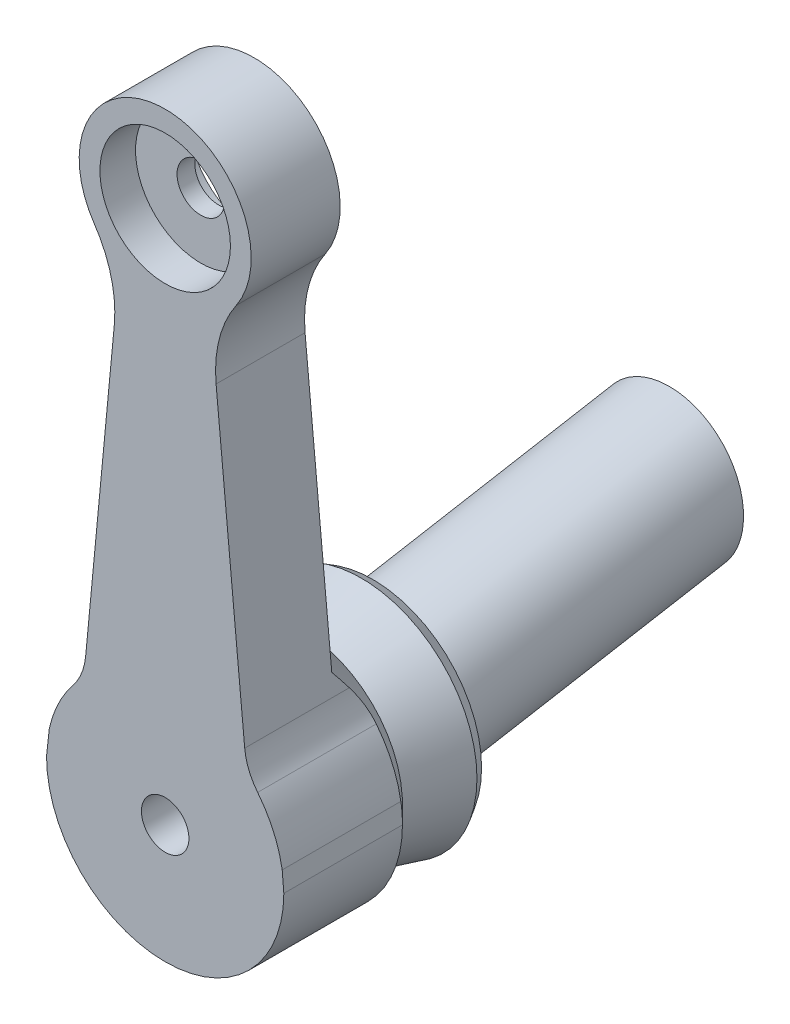
SolidWorks part; units mm, degrees
material "ABS"
ref_plane "Front Plane" through (0, 0, 0) normal (0, 0, 1) x (1, 0, 0)
ref_plane "Top Plane" through (0, 0, 0) normal (0, 1, 0) x (1, 0, 0)
ref_plane "Right Plane" through (0, 0, 0) normal (1, 0, 0) x (0, 0, -1)
sketch "Sketch2" plane through (0, 0, 0) normal (0, 0, 1) x (1, 0, 0)
  line L0 (0, 0) -> (0, 4) construction
  line L1 (19.7273, 3.2917) -> (20, 0)
  line L2 (0, 57.5) -> (0, 90) construction
  line L3 (-19.546, 4.2371) -> (-20, 0)
  line L4 (13.4071, 17.897) -> (7.9399, 75.3751)
  line L5 (-13.4071, 17.897) -> (-7.9399, 75.3751)
  arc A0 (-19.546, 4.2371) -> (19.7273, 3.2917) centre (0, 0) ccw
  circle A1 centre (0, 0) radius 4
  circle A2 centre (0, 90) radius 4
  arc A3 (12.5, 90) -> (-12.5, 90) centre (0, 90) ccw
  arc A4 (-15.5877, 12.531) -> (15.5877, 12.531) centre (0, 0) ccw
  arc A5 (9.9515, 82.4358) -> (-9.9515, 82.4358) centre (0, 90) ccw
  arc A6 (13.4071, 17.897) -> (15.5877, 12.531) centre (23.451, 18.8523) ccw
  arc A7 (-13.4071, 17.897) -> (-15.5877, 12.531) centre (-23.451, 18.8523) cw
  arc A8 (7.9399, 75.3751) -> (9.9515, 82.4358) centre (17.9838, 76.3305) cw
  arc A9 (-7.9399, 75.3751) -> (-9.9515, 82.4358) centre (-17.9838, 76.3305) ccw
  point P21 (13.7258, 14.5465)
  point P24 (-13.7258, 14.5465)
  point P27 (7.5, 80)
  point P30 (-7.5, 80)
  dimension "D1" = 40
  dimension "D2" = 8
  dimension "D4" = 8
  dimension "D5" = 25
  dimension "D6" = 25
  dimension "D8" = 10.0892
  dimension "D3" = 90
  dimension "D7" = 7.5
extrude "Boss-Extrude1" add sketch "Sketch2" along normal blind 15 contours L1 A3 L3 A0 A1 A2 region at (0.0012, 33.4788, 0)
sketch "Sketch3" plane through (0, 0, 0) normal (0, 0, -1) x (-1, 0, 0)
  circle A0 centre (0, 90) radius 11
  dimension "D1" = 22
extrude "Cut-Extrude1" cut sketch "Sketch3" against normal blind 6
sketch "Sketch4" plane through (0, 0, 15) normal (0, 0, 1) x (1, 0, 0)
  circle A0 centre (0, 90) radius 11
  dimension "D1" = 22
extrude "Cut-Extrude2" cut sketch "Sketch4" against normal blind 6
sketch "Sketch5" plane through (0, 0, 0) normal (0, 0, -1) x (-1, 0, 0)
  circle A0 centre (0, 0) radius 15
  dimension "D1" = 30
extrude "Boss-Extrude2" add sketch "Sketch5" along normal blind 20 draft 14 draft outward yes
chamfer "Chamfer1" distance 10 angle 45 1 edges at (15, 0, 0) first distance on face at (15, 0, 0)
chamfer "Chamfer2" distance 2 angle 45 1 edges at (-19.9866, 0, -20) first distance on face at (-16.9957, 0, -8.0043)
sketch "Sketch8" plane through (0, 0, -20) normal (0, 0, -1) x (-1, 0, 0)
  circle A0 centre (0, 0) radius 18.3367 construction
  point P0 (0, 0)
sketch "Sketch6" plane through (0, 0, 0) normal (1, 0, 0) x (0, 0, -1)
  line L0 (-7.5, 102.5) -> (-7.5, -42.3355) construction
  line L1 (0, 102.5) -> (-15, 102.5) construction
  line L3 (-15, 0) -> (5, 0) construction
  line L4 (-7.5, -4.849) -> (53.9902, 5.9934) construction
  dimension "D2" = 10
ref_plane "Plane1" through (0, -4.849, 7.5) normal (0, 0.1736, -0.9848) x (-1, 0, 0)
sketch "Sketch7" plane through (0, -4.849, 7.5) normal (0, 0.1736, -0.9848) x (-1, 0, 0)
  circle A0 centre (0, 0) radius 12.5
  dimension "D1" = 25
extrude "Boss-Extrude3" add sketch "Sketch7" along normal blind 100
sketch "Sketch9" plane through (0, 15.936, -90.3777) normal (0, 0.1736, -0.9848) x (-1, 0, 0)
  line L0 (0, -3.473) -> (0, 10.9995) construction
  line L1 (0, 10.9995) -> (0, -23.5749) construction
  circle A0 centre (0, -3.473) radius 12.5 construction
  circle A1 centre (0, 3.527) radius 2
  circle A2 centre (7, -3.473) radius 2
  circle A3 centre (0, -10.473) radius 2
  circle A4 centre (-7, -3.473) radius 2
  point P0 (0, -3.473)
  dimension "D1" = 4
  dimension "D3" = 7
  dimension "D2" = 4
extrude "Cut-Extrude3" cut sketch "Sketch9" against normal blind 40
sketch "Sketch10" plane through (0, 0, 0) normal (0, 0, 1) x (1, 0, 0)
  circle A0 centre (0, 12.5158) radius 17.2367
  ellipse E0 centre (0, 12.5158) end of major axis (12.5, 12.5158) minor radius 12.3101 construction
extrude "Cut-Extrude4" cut sketch "Sketch10" against normal blind 94 from offset 70 offset against normal yes
sketch "Sketch11" plane through (0, 0, 0) normal (0, 0, -1) x (-1, 0, 0)
  circle A1 centre (0, 90) radius 14.5
  arc A2 (-7.9399, 75.3751) -> (-9.9515, 82.4358) centre (-17.9838, 76.3305) ccw construction
  arc A3 (9.9515, 82.4358) -> (7.9399, 75.3751) centre (17.9838, 76.3305) ccw construction
  circle A4 centre (0, 90) radius 11
  point P5 (-8.0206, 77.9203)
  point P6 (8.0206, 77.9203)
extrude "Boss-Extrude4" add sketch "Sketch11" against normal up to surface (15 mm away) up to face at (11, 90, 15)
fillet "Fillet1" radius 20 2 edges at (-8.0206, 77.9203, 7.5) (8.0206, 77.9203, 7.5)
